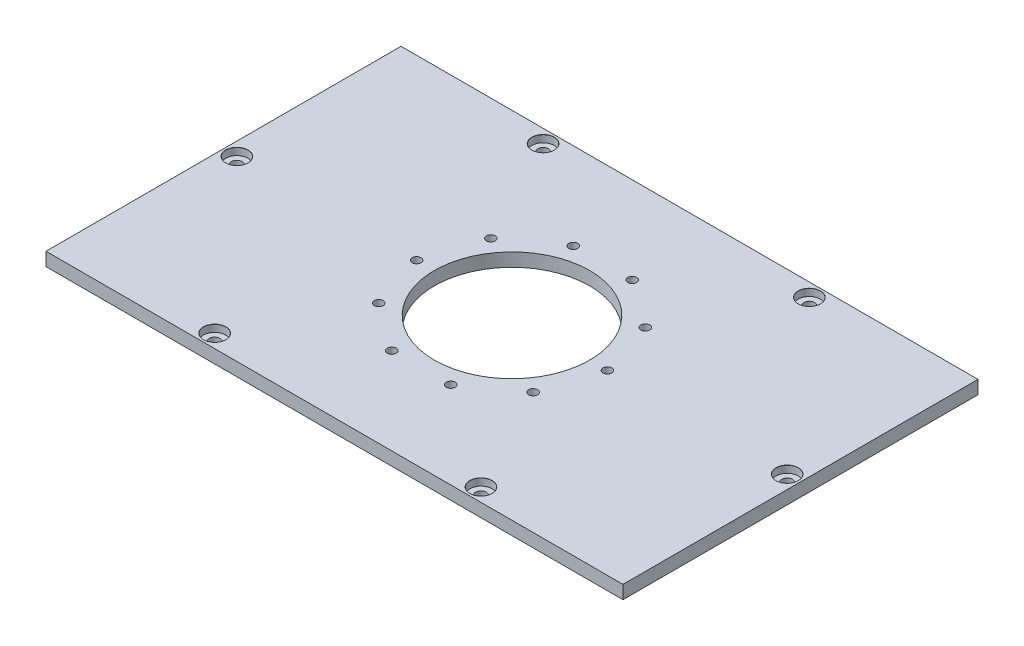
SolidWorks part; units mm, degrees
ref_plane "Ebene vorne" through (0, 0, 0) normal (0, 0, 1) x (1, 0, 0)
ref_plane "Ebene oben" through (0, 0, 0) normal (0, 1, 0) x (1, 0, 0)
ref_plane "Ebene rechts" through (0, 0, 0) normal (1, 0, 0) x (0, 0, -1)
sketch "Skizze1" plane through (0, 0, 0) normal (0, 1, 0) x (1, 0, 0)
  line L1 (0, 0) -> (130, 0)
  line L2 (0, 0) -> (0, 80)
  line L3 (0, 80) -> (130, 80)
  line L4 (130, 0) -> (130, 80)
  dimension "D1" = 80
  dimension "D2" = 130
extrude "Aufsatz-Linear austragen1" add sketch "Skizze1" along normal blind 3
hole_wizard "Ø2.4 (2.4) Durchmesser Bohrung1" positions "Skizze2" profile "Skizze3" hole size "Ø2.4" standard "DIN"
sketch "Skizze2" plane through (0, 3, 0) normal (0, 1, 0) x (1, 0, 0)
  line L0 (130, 80) -> (0, 80) construction
  line L1 (130, 0) -> (130, 80) construction
  line L2 (0, -3.3) -> (0, 3.3) construction
  line L3 (-3.3, 0) -> (3.3, 0) construction
  point P0 (35, 77)
  point P2 (95, 77)
  point P4 (127, 40)
  point P6 (95, 3)
  point P8 (35, 3)
  point P10 (3, 40)
  point P21 (133.0887, 32.8034)
  dimension "D1" = 3
  dimension "D2" = 3
  dimension "D3" = 3
  dimension "D4" = 3
  dimension "D5" = 3
  dimension "D6" = 3
  dimension "D7" = 35
  dimension "D8" = 35
  dimension "D9" = 35
  dimension "D10" = 35
  dimension "D11" = 40
  dimension "D12" = 40
sketch "Skizze3" plane through (35, 3, -77) normal (1, 0, 0) x (0, 0, 1)
  line L0 (0, 0) -> (0, 10.721)
  line L1 (0, 10.721) -> (1.2, 10)
  line L2 (1.2, 10) -> (1.2, 0.025)
  line L3 (1.2, 0.025) -> (1.225, 0)
  line L5 (1.225, 0) -> (0, 0)
  line L6 (-1.2, 0.025) -> (-1.225, 0) construction
  line L10 (0, 10.721) -> (-1.2, 10) construction
  line L11 (0, -6.35) -> (0, 107.95) construction
  dimension "Bohrerdurchmesser" = 2.4
  dimension "Bohrungstiefe" = 10
  dimension "Senkdurchmesser2 (Oben)" = 2.45
  dimension "Senkwinkel2 (Oben)" = 90
  dimension "Spitzenwinkel" = 118
hole_wizard "Stirnsenkung für M2 Flachkopfschraube mit Schlitz1" positions "Skizze6" profile "Skizze7" counterbore size "M2" standard "DIN"
sketch "Skizze6" plane through (0, 3, 0) normal (0, 1, 0) x (1, 0, 0)
  point P0 (95, 3)
  point P3 (127, 40)
  point P6 (95, 77)
  point P9 (35, 77)
  point P12 (3, 40)
  point P15 (35, 3)
sketch "Skizze7" plane through (95, 3, -3) normal (1, 0, 0) x (0, 0, 1)
  line L0 (0, 0) -> (0, 2.721)
  line L1 (0, 2.721) -> (1.2, 2)
  line L2 (1.2, 2) -> (1.2, 1.6)
  line L3 (1.2, 1.6) -> (2.5, 1.6)
  line L5 (2.5, 1.6) -> (2.5, 0.025)
  line L6 (2.5, 0.025) -> (2.525, 0)
  line L7 (2.525, 0) -> (0, 0)
  line L8 (-2.5, 0.025) -> (-2.525, 0) construction
  line L10 (0, 2.721) -> (-1.2, 2) construction
  line L11 (0, -6.35) -> (0, 107.95) construction
  dimension "Bohrerdurchmesser" = 2.4
  dimension "Bohrungstiefe" = 2
  dimension "Senkdurchmesser2" = 5
  dimension "Senktiefe2" = 1.6
  dimension "Senkdurchmesser4 (Oben)" = 5.05
  dimension "Senkwinkel2 (Oben)" = 90
  dimension "Spitzenwinkel" = 118
sketch "Skizze8" plane through (0, 3, 0) normal (0, 1, 0) x (1, 0, 0)
  line L0 (65, -24.4296) -> (65, 94.5281) construction
  line L1 (130, 0) -> (130, 80) construction
  line L3 (0, 80) -> (0, 0) construction
  line L4 (147.1504, 40) -> (-23.042, 40) construction
  line L5 (0, 0) -> (130, 0) construction
  line L6 (130, 80) -> (0, 80) construction
  circle A1 centre (47.6061, 52.6374) radius 1
  circle A2 centre (58.3561, 60.4477) radius 1
  circle A3 centre (71.6439, 60.4477) radius 1
  circle A4 centre (82.3939, 52.6374) radius 1
  circle A5 centre (86.5, 40) radius 1
  circle A6 centre (82.3939, 27.3626) radius 1
  circle A7 centre (71.6439, 19.5523) radius 1
  circle A8 centre (58.3561, 19.5523) radius 1
  circle A9 centre (47.6061, 27.3626) radius 1
  circle A10 centre (43.5, 40) radius 1
  circle A17 centre (65, 40) radius 17.5
  point P14 (65, 40)
  dimension "D1" = 2
  dimension "D3" = 43
  dimension "D11" = 35
  dimension "D2" = 10
extrude "Schnitt-Linear austragen1" cut sketch "Skizze8" against normal up to surface (3 mm away) up to face at (35, 0, -78.2)
